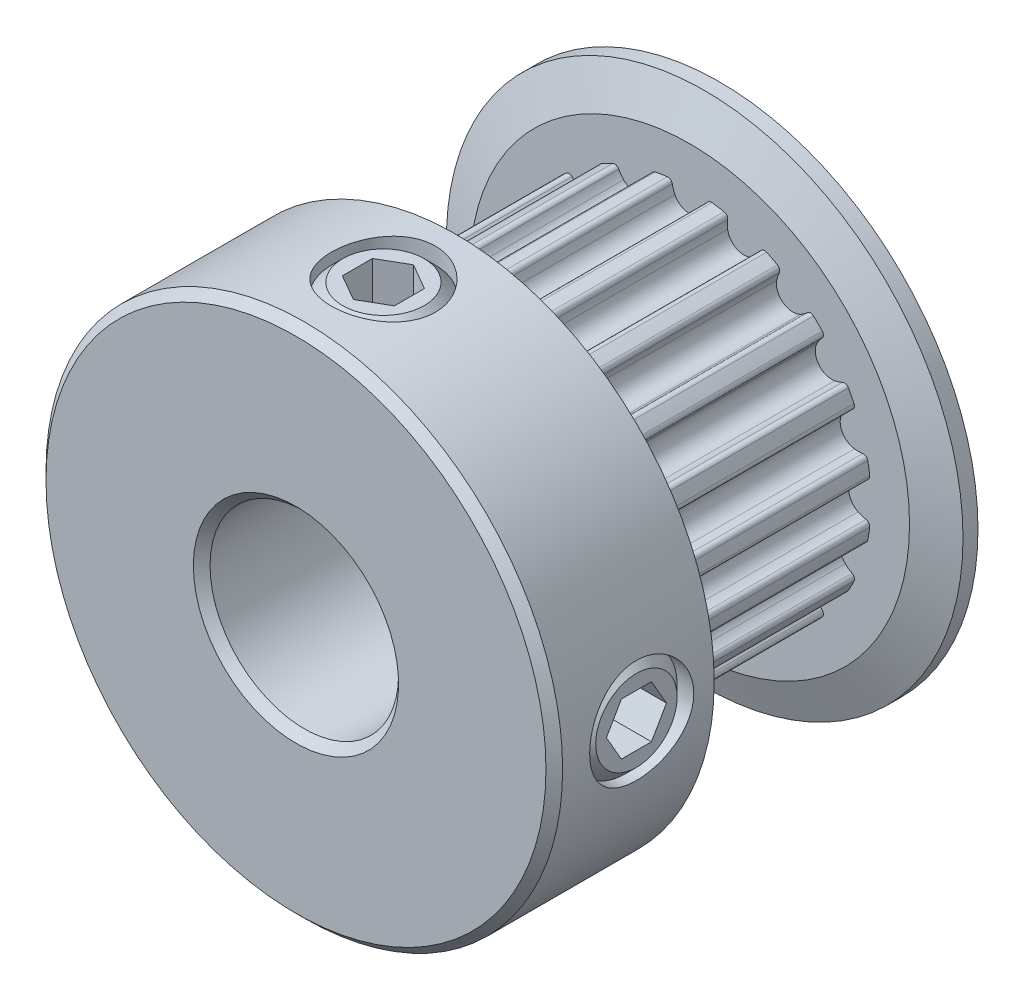
SolidWorks part; units mm, degrees
ref_plane "Front Plane" through (0, 0, 0) normal (0, 0, 1) x (1, 0, 0)
ref_plane "Top Plane" through (0, 0, 0) normal (0, 1, 0) x (1, 0, 0)
ref_plane "Right Plane" through (0, 0, 0) normal (1, 0, 0) x (0, 0, -1)
sketch "Sketch1" plane through (0, 0, 0) normal (0, 0, 1) x (1, 0, 0)
  line L1 (-1.7499, 5.3585) -> (1.7499, 5.3585) construction
  line L4 (0, 0) -> (0, 5.3585) construction
  line L5 (0, 5.3585) -> (0, 11.2112) construction
  line L6 (0, 6.3625) -> (1.9751, 6.0482) construction
  line L7 (1.9751, 6.0482) -> (2.6648, 5.8229) construction
  line L8 (1.9751, 6.0482) -> (1.7499, 5.3585) construction
  line L9 (-1.9751, 6.0482) -> (-1.7499, 5.3585) construction
  line L10 (-1.8963, 5.8067) -> (-2.841, 8.6995)
  line L11 (-2.841, 8.6995) -> (2.841, 8.6995)
  line L12 (2.841, 8.6995) -> (1.8963, 5.8067)
  circle A0 centre (0, 0) radius 6.3625 construction
  circle A1 centre (0, 0) radius 8.6995 construction
  circle A2 centre (0, 0) radius 6.1085 construction
  arc A3 (-0.4989, 5.6703) -> (0.4989, 5.6703) centre (0, 5.9135) ccw
  arc A4 (-0.4989, 5.6703) -> (-0.5855, 5.9387) centre (0.4, 6.1085) cw
  arc A5 (-1.8963, 5.8067) -> (-0.7518, 6.0621) centre (0, 0) cw
  arc A6 (-0.5855, 5.9387) -> (-0.7518, 6.0621) centre (-0.7333, 5.9132) ccw
  arc A7 (1.8963, 5.8067) -> (0.7518, 6.0621) centre (0, 0) ccw
  arc A8 (0.5855, 5.9387) -> (0.7518, 6.0621) centre (0.7333, 5.9132) cw
  arc A9 (0.4989, 5.6703) -> (0.5855, 5.9387) centre (-0.4, 6.1085) ccw
  point P6 (0, 20.9083)
  point P11 (0, 6.3625)
  point P13 (0, 8.6995)
  point P14 (0, 6.1085)
  dimension "D1" = 9.6972
  dimension "D2" = 4.8487
sketch "Sketch2" plane through (0, 0, 0) normal (1, 0, 0) x (0, 0, -1)
  line L0 (-7.135, 3.175) -> (7.135, 3.175)
  line L1 (-7.135, 3.175) -> (-7.135, 8.6995)
  line L2 (-1.75, 8.6995) -> (-7.135, 8.6995)
  line L3 (-2.255, 3.175) -> (-2.255, 8.6995) construction
  line L4 (-2.255, 8.6995) -> (-1.245, 8.6995) construction
  line L5 (-1.245, 8.6995) -> (-1.245, 6.1085) construction
  line L6 (-1.245, 6.1085) -> (6.125, 6.1085)
  line L7 (6.125, 6.1085) -> (6.125, 8.6995) construction
  line L8 (6.125, 8.6995) -> (7.135, 8.6995) construction
  line L9 (7.135, 8.6995) -> (7.135, 3.175)
  line L10 (-7.135, 0) -> (7.135, 0) construction
  line L11 (6.63, 8.6995) -> (6.125, 7.404)
  line L12 (-1.245, 7.404) -> (-1.75, 8.6995)
  line L14 (-1.245, 7.404) -> (-1.245, 6.1085)
  line L15 (6.125, 6.1085) -> (6.125, 7.404)
  line L16 (6.63, 8.6995) -> (7.135, 8.6995)
  arc A0 (-1.245, 7.404) -> (-1.75, 8.6995) centre (-3.1592, 7.404) ccw construction
  arc A1 (6.125, 7.404) -> (6.63, 8.6995) centre (8.0392, 7.404) cw construction
  point P12 (-1.245, 7.404)
  point P14 (-1.75, 8.6995)
  point P20 (6.125, 7.404)
  point P21 (6.63, 8.6995)
  point P25 (6.125, 0)
  point P26 (-1.245, 0)
  dimension "OA" = 14.27
  dimension "Bore" = 6.35
  dimension "Outside Width" = 8.38
  dimension "Inside Width" = 7.37
revolve "Revolve1" add sketch "Sketch2" angle 360 mid plane about L10
sketch "Sketch3" plane through (0, 0, 0) normal (0, 0, 1) x (1, 0, 0)
  line L6 (2.841, 8.6995) -> (-2.841, 8.6995)
  line L7 (1.8963, 5.8067) -> (2.841, 8.6995)
  line L8 (-2.841, 8.6995) -> (-1.8963, 5.8067)
  line L9 (2.841, 8.6995) -> (-2.841, 8.6995)
  line L10 (1.8963, 5.8067) -> (2.841, 8.6995)
  line L11 (-2.841, 8.6995) -> (-1.8963, 5.8067)
  arc A8 (1.8963, 5.8067) -> (0.7518, 6.0621) centre (0, 0) ccw
  arc A9 (0.7518, 6.0621) -> (0.5855, 5.9387) centre (0.7333, 5.9132) ccw
  arc A10 (0.4989, 5.6703) -> (0.5855, 5.9387) centre (-0.4, 6.1085) ccw
  arc A11 (-0.4989, 5.6703) -> (0.4989, 5.6703) centre (0, 5.9135) ccw
  arc A12 (-0.5855, 5.9387) -> (-0.4989, 5.6703) centre (0.4, 6.1085) ccw
  arc A13 (-0.5855, 5.9387) -> (-0.7518, 6.0621) centre (-0.7333, 5.9132) ccw
  arc A14 (-0.7518, 6.0621) -> (-1.8963, 5.8067) centre (0, 0) ccw
  arc A15 (1.8963, 5.8067) -> (0.7518, 6.0621) centre (0, 0) ccw
  arc A16 (0.7518, 6.0621) -> (0.5855, 5.9387) centre (0.7333, 5.9132) ccw
  arc A17 (0.4989, 5.6703) -> (0.5855, 5.9387) centre (-0.4, 6.1085) ccw
  arc A18 (-0.4989, 5.6703) -> (0.4989, 5.6703) centre (0, 5.9135) ccw
  arc A19 (-0.5855, 5.9387) -> (-0.4989, 5.6703) centre (0.4, 6.1085) ccw
  arc A20 (-0.5855, 5.9387) -> (-0.7518, 6.0621) centre (-0.7333, 5.9132) ccw
  arc A21 (-0.7518, 6.0621) -> (-1.8963, 5.8067) centre (0, 0) ccw
  dimension "D1" = 0
extrude "Cut-Extrude1" cut sketch "Sketch3" against normal up to vertex (6.125 mm away) from vertex up to point (0, 6.1085, -6.125) starting at point (0, 6.1085, 1.245)
pattern_circular "CirPattern1" count 20 over 360 about axis through (0, 0, 7.135) along (0, 0, 1) of "Cut-Extrude1"
sketch "Sketch4" plane through (0, 0, 0) normal (1, 0, 0) x (0, -1, 0)
  line L0 (0, -1.245) -> (0, -7.135) construction
  line L1 (-3.175, -7.135) -> (3.175, -7.135) construction
  line L2 (7.404, -1.245) -> (-7.404, -1.245) construction
  circle A0 centre (0, -4.19) radius 1.7526
extrude "Cut-Extrude2" cut sketch "Sketch4" along normal through all
ref_plane "Plane1" through (0, 0, 4.19) normal (0, 0, 1) x (1, 0, 0)
sketch "Sketch5" plane through (0, 0, 4.19) normal (0, 0, 1) x (1, 0, 0)
  line L0 (0, 0) -> (0, 8.6995) construction
  line L1 (3.175, -1.3716) -> (3.175, 0)
  line L2 (3.556, -1.7526) -> (8.1401, -1.7526)
  line L3 (3.175, 0) -> (8.6995, 0) construction
  line L4 (3.175, 0) -> (8.5211, 0)
  line L5 (8.5211, 0) -> (8.5211, -1.3716)
  line L6 (3.556, -1.7526) -> (3.175, -1.3716)
  line L7 (8.5211, -1.3716) -> (8.1401, -1.7526)
  circle A0 centre (0, 0) radius 8.6995 construction
  circle A1 centre (0, 0) radius 3.175 construction
  point P2 (3.175, -1.7526)
  point P11 (8.5211, -1.7526)
revolve "Revolve2" add sketch "Sketch5" angle 360 mid plane about L4
sketch "Sketch6" plane through (8.5211, 5.3841, 0) normal (-1, 0, 0) x (0, -1, 0)
  line L1 (5.3841, 5.2019) -> (4.5078, 4.6959)
  line L2 (4.5078, 4.6959) -> (4.5078, 3.6841)
  line L3 (4.5078, 3.6841) -> (5.3841, 3.1781)
  line L4 (5.3841, 3.1781) -> (6.2604, 3.6841)
  line L5 (6.2604, 3.6841) -> (6.2604, 4.6959)
  line L6 (6.2604, 4.6959) -> (5.3841, 5.2019)
  circle A0 centre (5.3841, 4.19) radius 0.8763 construction
  dimension "D1" = 1.7526
extrude "Cut-Extrude3" cut sketch "Sketch6" along normal blind 1.3144
pattern_circular "CirPattern3" count 2 over 90 about axis through (0, 0, 7.135) along (0, 0, 1) of "Cut-Extrude2", "Revolve2", "Cut-Extrude3"
chamfer "Chamfer1" distance 0.2807 angle 45 2 edges at (3.175, 0, 7.135) (8.6995, 0, 7.135)
ref_axis "Center Axis 1" through (0, 0, -7.135) along (0, 0, 1)
ref_plane "Contact Plane 1" through (0, 0, 7.135) normal (0, 0, 1) x (1, 0, 0)
ref_plane "Contact Plane 2" through (0, 0, -7.135) normal (0, 0, -1) x (-1, 0, 0)
equation "\"D2@Sketch1\"= \"D1@Sketch1\" / 2"
equation "\"D1@Sketch6\" = \"Set Screw@Sketch4\" / 2"
equation "\"D1@Cut-Extrude3\" = \"D1@Sketch6\"*.75"
